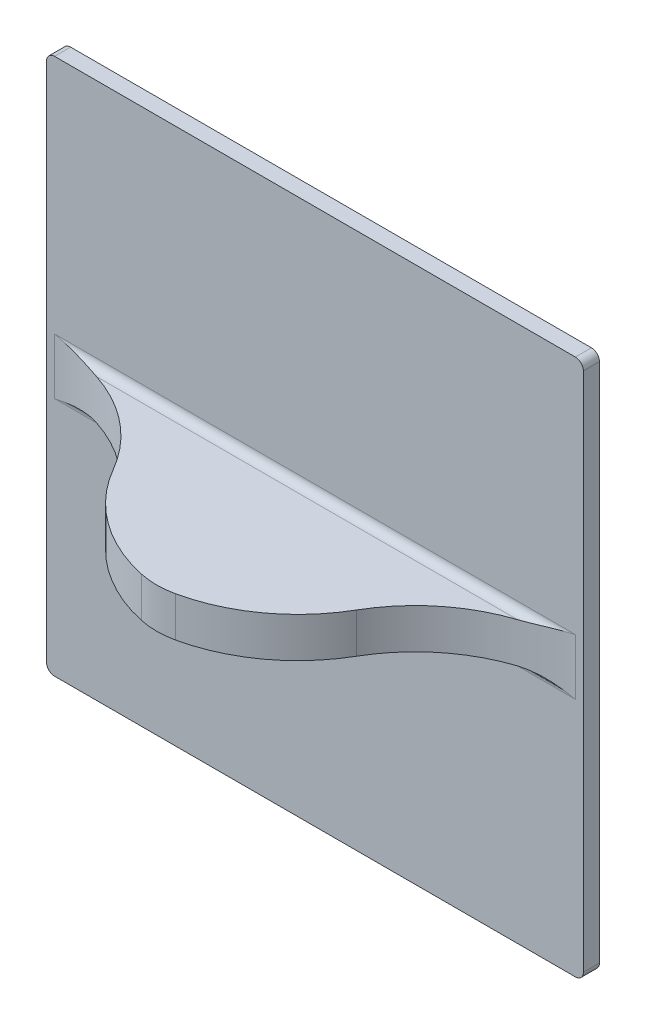
SolidWorks part; units mm, degrees
ref_plane "Ebene vorne" through (0, 0, 0) normal (0, 0, 1) x (1, 0, 0)
ref_plane "Ebene oben" through (0, 0, 0) normal (0, 1, 0) x (1, 0, 0)
ref_plane "Ebene rechts" through (0, 0, 0) normal (1, 0, 0) x (0, 0, -1)
sketch "Skizze1" plane through (0, 0, 0) normal (0, 0, 1) x (1, 0, 0)
  line L1 (-32.5, -33.5) -> (32.5, -33.5)
  line L2 (-33.5, -32.5) -> (-33.5, 32.5)
  line L3 (-32.5, 33.5) -> (32.5, 33.5)
  line L4 (33.5, -32.5) -> (33.5, 32.5)
  line L5 (-33.5, -33.5) -> (33.5, 33.5) construction
  line L6 (-33.5, 33.5) -> (33.5, -33.5) construction
  arc A0 (-33.5, -32.5) -> (-32.5, -33.5) centre (-32.5, -32.5) ccw
  arc A1 (32.5, -33.5) -> (33.5, -32.5) centre (32.5, -32.5) ccw
  arc A2 (33.5, 32.5) -> (32.5, 33.5) centre (32.5, 32.5) ccw
  arc A3 (-33.5, 32.5) -> (-32.5, 33.5) centre (-32.5, 32.5) cw
  point P0 (0, 0)
  dimension "D1" = 1
extrude "Aufsatz-Linear austragen1" add sketch "Skizze1" along normal blind 2
sketch "Skizze2" plane through (0, 0, 2) normal (0, 0, 1) x (1, 0, 0)
  line L1 (-12.5, -2.5) -> (12.5, -2.5)
  line L2 (-12.5, -2.5) -> (-12.5, 2.5)
  line L3 (-12.5, 2.5) -> (12.5, 2.5)
  line L4 (12.5, -2.5) -> (12.5, 2.5)
  line L5 (-12.5, -2.5) -> (12.5, 2.5) construction
  line L6 (-12.5, 2.5) -> (12.5, -2.5) construction
  point P0 (0, 0)
extrude "Aufsatz-Linear austragen2" add sketch "Skizze2" along normal blind 20
fillet "Verrundung1" radius 20 2 edges at (-12.5, 0, 2) (12.5, 0, 2)
fillet "Verrundung2" radius 1 2 edges at (0, -2.5, 2) (0, 2.5, 2)
fillet "Verrundung3" radius 20 2 edges at (-12.5, 0, 22) (12.5, 0, 22)
fillet "Verrundung4" radius 10 1 edges at (0, 0, 21.8851)
